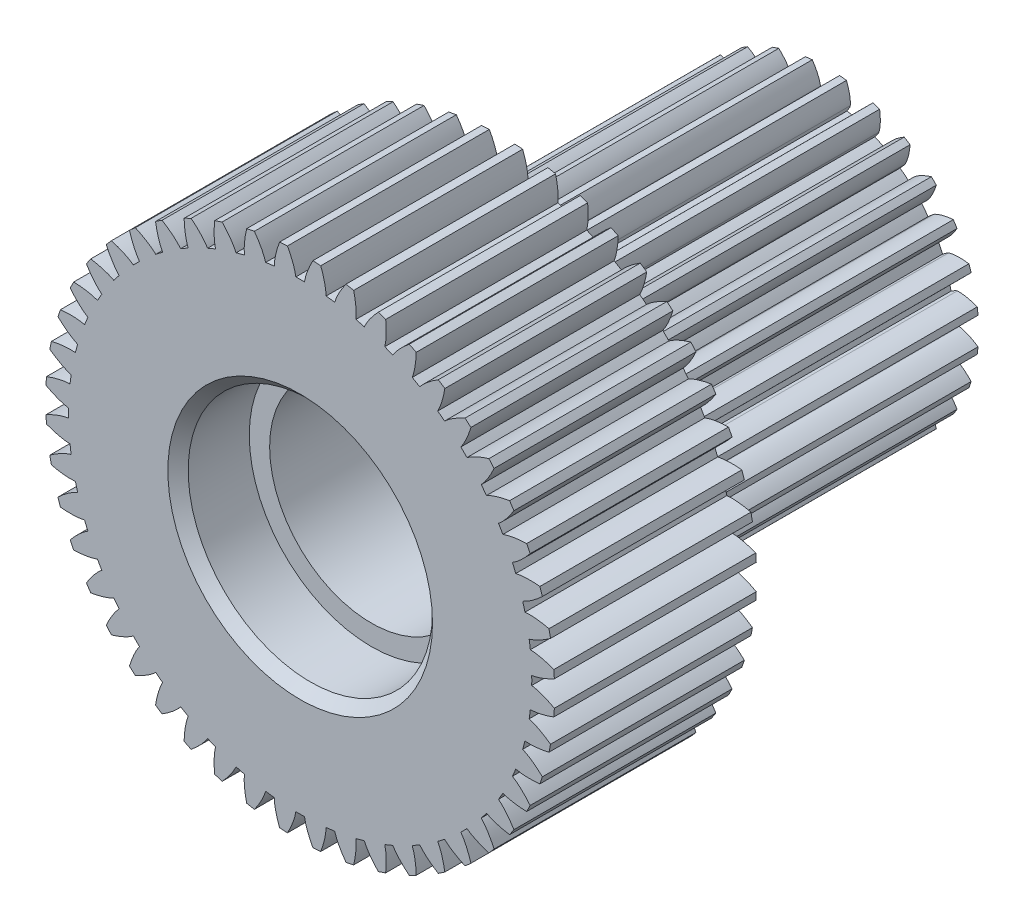
SolidWorks part; units mm, degrees
material "PLA"
ref_plane "Front Plane" through (0, 0, 0) normal (0, 0, 1) x (1, 0, 0)
ref_plane "Top Plane" through (0, 0, 0) normal (0, 1, 0) x (1, 0, 0)
ref_plane "Right Plane" through (0, 0, 0) normal (1, 0, 0) x (0, 0, -1)
sketch "Sketch1" plane through (0, 0, 0) normal (0, 0, 1) x (1, 0, 0)
  circle A0 centre (0, 0) radius 12.5
  dimension "D1" = 25
extrude "Boss-Extrude1" add sketch "Sketch1" along normal mid plane 9.918
sketch "Sketch2" plane through (0, 0, 0) normal (0, 0, 1) x (1, 0, 0)
  line L0 (0, 0) -> (11.9981, 0.2138) construction
  line L1 (0, 0) -> (12, 0) construction
  line L2 (0, 0) -> (11.9981, -0.2138) construction
  line L3 (11.2721, -0.2009) -> (11.3732, -0.2027)
  line L4 (11.2745, 0.2009) -> (11.3732, 0.2027)
  circle A0 centre (0, 0) radius 12 construction
  circle A1 centre (0, 0) radius 11.2763 construction
  circle A2 centre (0, 0) radius 11.375
  circle A3 centre (0, 0) radius 12.5 construction
  circle A4 centre (0, 0) radius 12.5
  spline S0 degree 4 poles (11.2745, 0.2009) (11.2784, 0.2011) (11.2892, 0.2016) (11.3096, 0.2032) (11.3428, 0.2069) (11.385, 0.213) (11.4394, 0.2225) (11.5033, 0.2357) (11.5732, 0.2525) (11.6488, 0.273) (11.724, 0.2956) (11.7986, 0.32) (11.8726, 0.346) (11.9619, 0.3795) (12.0682, 0.4225) (12.1915, 0.4768) (12.3302, 0.5432) (12.47, 0.6159) (12.6064, 0.6915) (12.7427, 0.7727) (12.8735, 0.8545) (13.0077, 0.9443) (13.1307, 1.0295) (13.2665, 1.1303) (13.3755, 1.213) (13.5171, 1.3277) (13.6, 1.3971) (13.6963, 1.4801) (13.7386, 1.5179) (13.7646, 1.5412) knots 0 0 0 0 0 0.005377 0.015084 0.028532 0.04661 0.064855 0.092111 0.119476 0.146842 0.174209 0.201575 0.228941 0.256307 0.307035 0.361767 0.4165 0.471232 0.525964 0.580697 0.635429 0.690161 0.744894 0.799626 0.854358 0.909091 0.954545 1 1 1 1 1 construction
  spline S1 degree 4 poles (11.2745, 0.2009) (11.2784, 0.2011) (11.2892, 0.2016) (11.3096, 0.2032) (11.3428, 0.2069) (11.385, 0.213) (11.4394, 0.2225) (11.5033, 0.2357) (11.5732, 0.2525) (11.6488, 0.273) (11.724, 0.2956) (11.7986, 0.32) (11.8726, 0.346) (11.9619, 0.3795) (12.0682, 0.4225) (12.1915, 0.4768) (12.3302, 0.5432) (12.47, 0.6159) (12.6064, 0.6915) (12.7427, 0.7727) (12.8735, 0.8545) (13.0077, 0.9443) (13.1307, 1.0295) (13.2665, 1.1303) (13.3755, 1.213) (13.4864, 1.3028) (13.5401, 1.3472) (13.5674, 1.3701) knots 0 0 0 0 0 0.005377 0.015084 0.028532 0.04661 0.064855 0.092111 0.119476 0.146842 0.174209 0.201575 0.228941 0.256307 0.307035 0.361767 0.4165 0.471232 0.525964 0.580697 0.635429 0.690161 0.744894 0.799626 0.854358 0.909091 0.909091 0.909091 0.909091 0.909091
  spline S2 degree 4 poles (11.2721, -0.2009) (11.2759, -0.201) (11.2867, -0.2015) (11.3071, -0.2032) (11.3403, -0.2069) (11.3825, -0.213) (11.437, -0.2224) (11.5008, -0.2357) (11.5707, -0.2524) (11.6464, -0.273) (11.7216, -0.2955) (11.7962, -0.3199) (11.8702, -0.3459) (11.9594, -0.3795) (12.0658, -0.4225) (12.1891, -0.4768) (12.3277, -0.5432) (12.4676, -0.6158) (12.604, -0.6915) (12.7403, -0.7726) (12.8711, -0.8545) (13.0052, -0.9442) (13.1282, -1.0295) (13.264, -1.1302) (13.373, -1.213) (13.5146, -1.3277) (13.5975, -1.397) (13.6938, -1.48) (13.7361, -1.5179) (13.7622, -1.5412) knots 0 0 0 0 0 0.005377 0.015084 0.028532 0.04661 0.064855 0.092111 0.119476 0.146842 0.174209 0.201575 0.228941 0.256307 0.307035 0.361767 0.4165 0.471232 0.525964 0.580697 0.635429 0.690161 0.744894 0.799626 0.854358 0.909091 0.954545 1 1 1 1 1 construction
  spline S3 degree 4 poles (11.2721, -0.2009) (11.2759, -0.201) (11.2867, -0.2015) (11.3071, -0.2032) (11.3403, -0.2069) (11.3825, -0.213) (11.437, -0.2224) (11.5008, -0.2357) (11.5707, -0.2524) (11.6464, -0.273) (11.7216, -0.2955) (11.7962, -0.3199) (11.8702, -0.3459) (11.9594, -0.3795) (12.0658, -0.4225) (12.1891, -0.4768) (12.3277, -0.5432) (12.4676, -0.6158) (12.604, -0.6915) (12.7403, -0.7726) (12.8711, -0.8545) (13.0052, -0.9442) (13.1282, -1.0295) (13.264, -1.1302) (13.373, -1.213) (13.4839, -1.3028) (13.5376, -1.3471) (13.565, -1.3701) knots 0 0 0 0 0 0.005377 0.015084 0.028532 0.04661 0.064855 0.092111 0.119476 0.146842 0.174209 0.201575 0.228941 0.256307 0.307035 0.361767 0.4165 0.471232 0.525964 0.580697 0.635429 0.690161 0.744894 0.799626 0.854358 0.909091 0.909091 0.909091 0.909091 0.909091
  dimension "D1" = 24
  dimension "D2" = 22.5526
  dimension "D3" = 22.75
  dimension "D4" = 1.021
  dimension "D5" = 1.021
extrude "Cut-Extrude1" cut sketch "Sketch2" against normal through all both and the other way through all contours A2 A4 region at (12.0369, -0.0005, 0)
pattern_circular "CirPattern2" count 48 over 360 about axis through (0, 0, 4.959) along (0, 0, -1) of "Cut-Extrude1"
sketch "Sketch3" plane through (0, 0, 4.959) normal (0, 0, 1) x (1, 0, 0)
  circle A0 centre (0, 0) radius 5
  dimension "D1" = 10
sketch "Sketch4" plane through (0, 0, -4.959) normal (0, 0, -1) x (-1, 0, 0)
  circle A0 centre (0, 0) radius 7.5
  dimension "D1" = 15
extrude "Boss-Extrude2" add sketch "Sketch4" along normal blind 15.9054
sketch "Sketch5" plane through (0, 0, -20.8644) normal (0, 0, -1) x (-1, 0, 0)
  line L0 (0, 0) -> (7.5, 0) construction
  line L1 (0, 0) -> (7.4936, 0.3089) construction
  line L2 (0, 0) -> (7.4936, -0.3089) construction
  line L3 (6.5519, 0.2701) -> (6.3696, 0.2625)
  line L4 (6.5519, -0.2701) -> (6.3696, -0.2625)
  circle A0 centre (0, 0) radius 6.5778 construction
  circle A1 centre (0, 0) radius 6.375
  arc A2 (7.47, -0.67) -> (7.47, 0.67) centre (0, 0) ccw
  spline S0 degree 4 poles (6.5519, 0.2701) (6.5542, 0.2702) (6.5605, 0.2706) (6.5799, 0.2727) (6.618, 0.2785) (6.6647, 0.2883) (6.7181, 0.302) (6.7693, 0.3172) (6.8128, 0.3314) (6.856, 0.3466) (6.8988, 0.3628) (6.9503, 0.3836) (7.0118, 0.4101) (7.083, 0.4435) (7.1629, 0.4841) (7.2435, 0.5284) (7.322, 0.5743) (7.4004, 0.6235) (7.4755, 0.673) (7.5525, 0.7272) (7.6231, 0.7786) (7.7009, 0.8392) (7.7634, 0.8889) (7.8444, 0.9577) (7.8918, 0.9993) (7.9468, 1.049) (7.971, 1.0717) (7.9858, 1.0856) knots 0 0 0 0 0 0.005377 0.015084 0.04661 0.092111 0.119476 0.146842 0.174209 0.201575 0.228941 0.256307 0.307035 0.361767 0.4165 0.471232 0.525964 0.580697 0.635429 0.690161 0.744894 0.799626 0.854358 0.909091 0.954545 1 1 1 1 1 construction
  spline S1 degree 4 poles (6.5519, 0.2701) (6.5542, 0.2702) (6.5605, 0.2706) (6.5799, 0.2727) (6.618, 0.2785) (6.6647, 0.2883) (6.7181, 0.302) (6.7693, 0.3172) (6.8128, 0.3314) (6.856, 0.3466) (6.8988, 0.3628) (6.9503, 0.3836) (7.0118, 0.4101) (7.083, 0.4435) (7.1629, 0.4841) (7.2435, 0.5284) (7.322, 0.5743) (7.4004, 0.6235) (7.4755, 0.673) (7.5525, 0.7272) (7.6231, 0.7786) (7.7009, 0.8392) (7.7634, 0.8889) (7.8268, 0.9428) (7.8575, 0.9694) (7.8732, 0.9832) knots 0 0 0 0 0 0.005377 0.015084 0.04661 0.092111 0.119476 0.146842 0.174209 0.201575 0.228941 0.256307 0.307035 0.361767 0.4165 0.471232 0.525964 0.580697 0.635429 0.690161 0.744894 0.799626 0.854358 0.909091 0.909091 0.909091 0.909091 0.909091
  spline S2 degree 4 poles (6.5519, -0.2701) (6.5542, -0.2702) (6.5605, -0.2706) (6.5799, -0.2727) (6.618, -0.2785) (6.6647, -0.2883) (6.7181, -0.302) (6.7693, -0.3172) (6.8128, -0.3314) (6.856, -0.3466) (6.8988, -0.3628) (6.9503, -0.3836) (7.0118, -0.4101) (7.083, -0.4435) (7.1629, -0.4841) (7.2435, -0.5284) (7.322, -0.5743) (7.4004, -0.6235) (7.4755, -0.673) (7.5525, -0.7272) (7.6231, -0.7786) (7.7009, -0.8392) (7.7634, -0.8889) (7.8444, -0.9577) (7.8918, -0.9993) (7.9468, -1.049) (7.971, -1.0717) (7.9858, -1.0856) knots 0 0 0 0 0 0.005377 0.015084 0.04661 0.092111 0.119476 0.146842 0.174209 0.201575 0.228941 0.256307 0.307035 0.361767 0.4165 0.471232 0.525964 0.580697 0.635429 0.690161 0.744894 0.799626 0.854358 0.909091 0.954545 1 1 1 1 1 construction
  spline S3 degree 4 poles (6.5519, -0.2701) (6.5542, -0.2702) (6.5605, -0.2706) (6.5799, -0.2727) (6.618, -0.2785) (6.6647, -0.2883) (6.7181, -0.302) (6.7693, -0.3172) (6.8128, -0.3314) (6.856, -0.3466) (6.8988, -0.3628) (6.9503, -0.3836) (7.0118, -0.4101) (7.083, -0.4435) (7.1629, -0.4841) (7.2435, -0.5284) (7.322, -0.5743) (7.4004, -0.6235) (7.4755, -0.673) (7.5525, -0.7272) (7.6231, -0.7786) (7.7009, -0.8392) (7.7634, -0.8889) (7.8268, -0.9428) (7.8575, -0.9694) (7.8732, -0.9832) knots 0 0 0 0 0 0.005377 0.015084 0.04661 0.092111 0.119476 0.146842 0.174209 0.201575 0.228941 0.256307 0.307035 0.361767 0.4165 0.471232 0.525964 0.580697 0.635429 0.690161 0.744894 0.799626 0.854358 0.909091 0.909091 0.909091 0.909091 0.909091
  dimension "D2" = 12.75
  dimension "D3" = 15
  dimension "D1" = 13.1557
  dimension "D4" = 2.36
  dimension "D5" = 2.36
extrude "Cut-Extrude2" cut sketch "Sketch5" against normal up to surface (15.9054 mm away) contours A2 A1 region at (-7.0303, 0, -20.8644) up to face at (7.5, 0, -4.959)
pattern_circular "CirPattern3" count 28 over 360 about axis through (0, 0, -20.8644) along (0, 0, 1) of "Cut-Extrude2"
extrude "Cut-Extrude3" cut sketch "Sketch3" against normal through all contours A0
sketch "Sketch7" plane through (0, 0, -20.8644) normal (0, 0, -1) x (-1, 0, 0)
  circle A0 centre (0, 0) radius 6
  dimension "D1" = 12
extrude "Cut-Extrude4" cut sketch "Sketch7" against normal blind 3.5
ref_plane "Plane1" through (0, 0, -7.9527) normal (0, 0, -1) x (-1, 0, 0)
mirror "Mirror1" about plane through (0, 0, -7.9527) normal (0, 0, -1) of "Cut-Extrude4"
chamfer "Chamfer1" distance 0.5 angle 45 2 edges at (-6, 0, 4.959) (-6, 0, -20.8644)
equation "\"module\" = 0.5"
equation "\"pressure angle\" = 20.0"
equation "\"h_a\" = 0.5"
equation "\"h_b\" = 0.625"
equation "\"clr_tip_root\" = 0.125"
equation "\"D1@Sketch1\" = \"dp_p_b\" + 2 * \"h_a\""
equation "\"D1@Boss-Extrude1\" = \"fw_p_b\""
equation "\"D1@Sketch2\" = \"dp_p_b\""
equation "\"D2@Sketch2\"= \"db_p_b\""
equation "\"D3@Sketch2\" = \"dp_p_b\" - 2 * \"h_b\""
equation "\"Nr_s\" = 132"
equation "\"pressure_angle\" = 20.0"
equation "\"h_f\" = 0.625"
equation "\"dp_r_s\" = 66.0"
equation "\"bearing_ID\" = 60"
equation "\"bearing_OD\" = 78"
equation "\"bearing_height\" = 10"
equation "\"clearance_planet\" = 1.5"
equation "\"case_dist\" = 6.5"
equation "\"Motor_case_OD_max\" = 111.3"
equation "\"case_mounting_PCD\" = 103.8"
equation "\"bearing mount thickness\" = 8"
equation "\"case_mounting_hole_dia\" = 3"
equation "\"output_mounting_PCD\" = 86"
equation "\"output_mounting_hole_dia\" = 4"
equation "\"clearance_case_mount_holes_shell_thickness\" = 1"
equation "\"motor_case_OD_base\" = 101.8"
equation "\"sec_carrier_thickness\" = 5"
equation "\"sun_coupler_hub_thickness\" = 4"
equation "\"clearance_sun_coupler_sec_carrier\" = 1.5"
equation "\"clearance_motor_and_case\" = 5"
equation "\"motor_OD\" = 86.8"
equation "\"Motor_case_thickness\" = 2.5"
equation "\"Motor_case_ID\" = 96.8"
equation "\"case_mounting_hole_shift\" = 1.0"
equation "\"output_mounting_nut_wrench_size\" = 7"
equation "\"output_mounting_nut_thickness\" = 3.2"
equation "\"case_mounting_hole_allen_socket_dia\" = 5.5"
equation "\"output_mounting_nut_depth\" = 3"
equation "\"case_mounting_bolt_depth\" = 4.5"
equation "\"Ns\" = 56"
equation "\"ring_radial_thickness\" = 5"
equation "\"ring_to_chamfer_clearance\" = 1.5"
equation "\"Motor_case_OD_base_to_chamfer\" = 5"
equation "\"pattern_offset_from_motor_case_OD_base\" = 3"
equation "\"pattern_bulge_dia\" = 3"
equation "\"pattern_num_bulge\" = 18"
equation "\"pattern_depth\" = 2"
equation "\"motor_height\" = 26.5"
equation "\"case_mounting_wrench_size\" = 5.5"
equation "\"case_mounting_nut_clearance\" = 2"
equation "\"base_plate_thickness\" = 4"
equation "\"case_mounting_nut_thickness\" = 2.4"
equation "\"case_mounting_surface_height\" = 4"
equation "\"motor_mount_hole_PCD\" = 32"
equation "\"motor_mount_hole_dia\" = 4"
equation "\"motor_mount_hole_num\" = 4"
equation "\"central_hole_offset_from_motor_mount_PCD\" = 5"
equation "\"wire_slot_dist_from_center\" = 38"
equation "\"wire_slot_length\" = 10"
equation "\"wire_slot_radius\" = 2.5"
equation "\"driver_upper_holes_dist_from_center\" = 29"
equation "\"driver_lower_holes_dist_from_center\" = 13"
equation "\"driver_side_holes_dist_from_center\" = 22.5"
equation "\"driver_mount_holes_dia\" = 3"
equation "\"driver_mount_inserts_OD\" = 4.8"
equation "\"driver_mount_thickness\" = 1.5"
equation "\"driver_mount_height\" = 6"
equation "\"air_flow_hole_offset\" = 3"
equation "\"num_planet\" = 4"
equation "\"planet_pin_bolt_dia\" = 5"
equation "\"planet_pin_socket_head_dia\" = 8.5"
equation "\"carrier_PCD\" = 52.0"
equation "\"planet_shaft_dia\" = 8"
equation "\"planet_shaft_step_offset\" = 1"
equation "\"carrier_trapezoidal_support_sun_offset\" = 5"
equation "\"carrier_trapezoidal_support_hole_PCD_offset_bearing_ID\" = 4"
equation "\"carrier_trapezoidal_support_hole_dia\" = 3"
equation "\"carrier_trapezoidal_support_hole_socket_head_dia\" = 5.5"
equation "\"carrier_bearing_step_width\" = 1.5"
equation "\"standard_clearance_1_5mm\" = 1.5"
equation "\"standard_fillet_1_5mm\" = 1.5"
equation "\"sun_shaft_bearing_OD\" = 16"
equation "\"sun_shaft_bearing_width\" = 5"
equation "\"standard_bearing_insertion_chamfer\" = 0.5"
equation "\"carrier_trapezoidal_support_hole_wrench_size\" = 5.5"
equation "\"planet_pin_bolt_wrench_size\" = 8"
equation "\"planet_bearing_OD\" = 12"
equation "\"planet_bearing_width\" = 3.5"
equation "\"planet_bore\" = 10"
equation "\"D1@Sketch3\"=\"planet_bore\""
equation "\"Np_b\" = 48"
equation "\"dp_s\" = 28.0"
equation "\"db_s\" = 26.311393382005434"
equation "\"fw_s_calc\" = 2.7970255760332914"
equation "\"alpha_s\" = 0.8539582918412485"
equation "\"beta_s\" = 1.5063691306032174"
equation "\"dp_p_b\" = 24.0"
equation "\"db_p_b\" = 22.552622898861802"
equation "\"fw_p_s\" = 15.90536252346366"
equation "\"alpha_p_b\" = 0.8539582918412414"
equation "\"beta_p_b\" = 2.042083416317517"
equation "\"motor_output_hole_PCD\" = 23"
equation "\"motor_output_hole_dia\" = 4"
equation "\"motor_output_hole_num\" = 4"
equation "\"sun_shaft_bearing_ID\" = 8"
equation "\"sun_hub_dia\" = 30.0"
equation "\"sun_central_bolt_dia\" = 5"
equation "\"sun_central_bolt_socket_head_dia\" = 8.5"
equation "\"fw_s_used\" = 33.32338113475014"
equation "\"motor_output_hole_CSK_OD\" = 8"
equation "\"motor_output_hole_CSK_head_height\" = 2.0"
equation "\"bearing_retainer_thickness\" = 2"
equation "\"Np_s\" = 28"
equation "\"fw_p_b\" = 9.918018611286483"
equation "\"dp_p_s\" = 14.0"
equation "\"db_p_s\" = 13.155696691002717"
equation "\"alpha_p_s\" = 0.8539582918412485"
equation "\"beta_p_s\" = 4.720654844888932"
equation "\"D1@Sketch4\"=\"dp_p_s\" + 2 * \"h_a\""
equation "\"D1@Boss-Extrude2\"=\"fw_p_s\""
equation "\"D2@Sketch5\"=\"dp_p_s\" - 2 * \"h_b\""
equation "\"D3@Sketch5\"=\"dp_p_s\"+2 * \"h_a\" "
equation "\"D1@Sketch5\"=\"db_p_s\""
equation "\"D1@CirPattern3\"=\"Np_s\""
equation "\"D4@Sketch5\"=\"beta_p_s\"/2"
equation "\"D5@Sketch5\"=\"beta_p_s\"/2"
equation "\"D4@Sketch2\"=\"beta_p_b\"/2"
equation "\"D5@Sketch2\"=\"beta_p_b\"/2"
equation "\"D1@Sketch7\"=\"planet_bearing_OD\""
equation "\"D1@Cut-Extrude4\"=\"planet_bearing_width\""
equation "\"D1@Chamfer1\"=\"standard_bearing_insertion_chamfer\""
equation "\"D1@CirPattern2\"=\"Np_b\""
equation "\"Nr_b\" = 152"
equation "\"dp_r_b\" = 76.0"
equation "\"db_r_b\" = 71.41663917972905"
equation "\"fw_r_b\" = 9.918018611286483"
equation "\"alpha_r_b\" = 0.8539582918412236"
equation "\"beta_r_b\" = 2.8921271099982366"
equation "\"ring_OD_b\" = 86.0"
equation "\"Fillet10\"= IIF ( \"ring_OD_b\" > ( \"bearing_OD\" + 2 * \"bearing mount thickness\" ) , \"suppressed\" , \"unsuppressed\" )"
equation "\"Fillet11\"= IIF ( \"ring_OD_b\" < ( \"bearing_OD\" + 2 * \"bearing mount thickness\" ) , \"suppressed\" , \"unsuppressed\" )"
equation "\"clr_tip_root_s\" = 0.125"
equation "\"db_r_s\" = 62.01971297186996"
equation "\"fw_r_s\" = 14.40536252346366"
equation "\"alpha_r_s\" = 0.8539582918412449"
equation "\"beta_r_s\" = 3.071552947318853"
equation "\"small_ring_case_thickness\" = 4"
equation "\"carrier_thickness\" = 4"
equation "\"small_ring_output_wall_thickness\" = 5"
equation "\"small_ring_output_wall_to_bearing_shaft_attachement_hole_dia\" = 4"
equation "\"small_ring_output_wall_to_bearing_shaft_attachement_hole_depth\" = 6.5"
equation "\"small_ring_output_wall_to_bearing_shaft_attachement_nut_wrench\" = 7"
equation "\"small_ring_output_wall_to_bearing_shaft_attachement_nut_thickness\" = 3.2"
equation "\"small_ring_output_wall_to_bearing_shaft_attachement_hole_pcd\" = 12"
equation "\"small_ring_output_wall_to_bearing_shaft_attachement_hole_num\" = 3"
equation "\"small_ring_output_wall_to_bearing_shaft_attachement_hole_CSK_OD\" = 8"
equation "\"small_ring_output_wall_to_bearing_shaft_attachement_hole_CSK_head_height\" = 2.0"
equation "\"carrier_small_ring_inner_bearing_ID\" = 20"
equation "\"carrier_small_ring_inner_bearing_OD\" = 32"
equation "\"carrier_small_ring_inner_bearing_height\" = 7"
equation "\"carrier_small_ring_inner_bearing_flap\" = 2"
equation "\"gear_casing_big_ring_to_bearing_dist\" = 24.90536252346366"
equation "\"gear_casing_thickness\" = 4"
